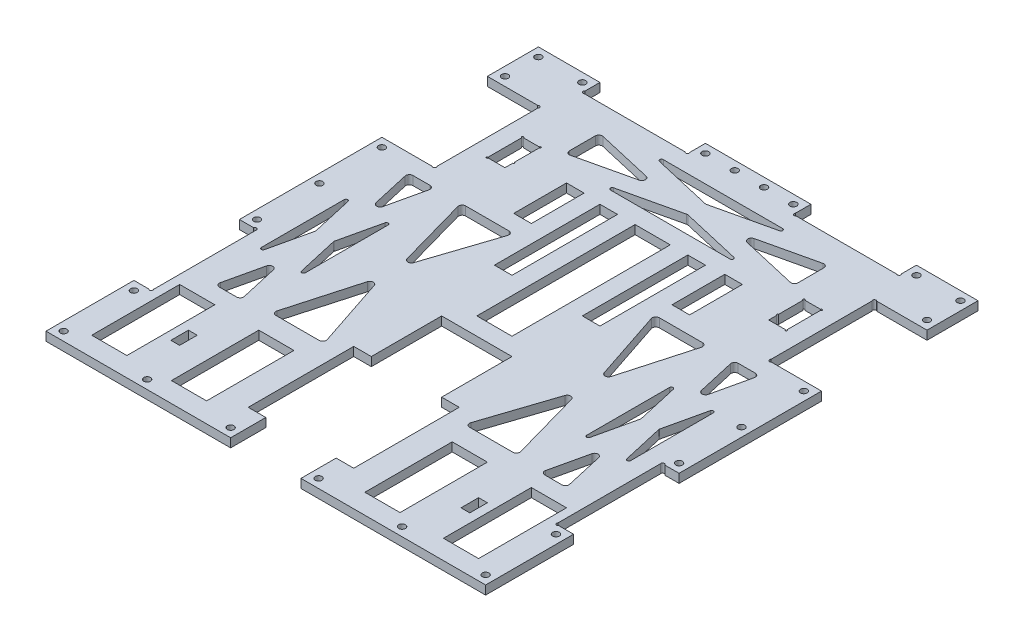
SolidWorks part; units mm, degrees
material "7050-T73510"
ref_plane "Front Plane" through (0, 0, 0) normal (0, 0, 1) x (1, 0, 0)
ref_plane "Top Plane" through (0, 0, 0) normal (0, 1, 0) x (1, 0, 0)
ref_plane "Right Plane" through (0, 0, 0) normal (1, 0, 0) x (0, 0, -1)
sketch "Sketch1" plane through (0, 0, 0) normal (0, 1, 0) x (1, 0, 0)
  line L1 (-158.75, -177.8) -> (158.75, -177.8)
  line L2 (-158.75, -177.8) -> (-158.75, 177.8)
  line L3 (-158.75, 177.8) -> (158.75, 177.8)
  line L4 (158.75, -177.8) -> (158.75, 177.8)
  line L5 (-158.75, -177.8) -> (158.75, 177.8) construction
  line L6 (-158.75, 177.8) -> (158.75, -177.8) construction
  point P0 (0, 0)
  dimension "D1" = 355.6
  dimension "D2" = 317.5
extrude "Boss-Extrude1" add sketch "Sketch1" along normal blind 6.35
sketch "Sketch2" plane through (0, 6.35, 0) normal (0, 1, 0) x (1, 0, 0)
  line L0 (-158.75, -177.8) -> (158.75, -177.8) construction
  line L1 (-25.4, -25.4) -> (25.4, -25.4)
  line L2 (-25.4, -25.4) -> (-25.4, -177.8)
  line L3 (-25.4, -177.8) -> (25.4, -177.8)
  line L4 (25.4, -25.4) -> (25.4, -177.8)
  line L5 (-25.4, -25.4) -> (25.4, -177.8) construction
  line L6 (-25.4, -177.8) -> (25.4, -25.4) construction
  point P0 (0, -101.6)
  dimension "D1" = 152.4
  dimension "D2" = 50.8
extrude "Cut-Extrude1" cut sketch "Sketch2" against normal through all
sketch "Sketch3" plane through (0, 6.35, 0) normal (0, 1, 0) x (1, 0, 0)
  line L0 (158.75, -177.8) -> (158.75, 177.8) construction
  line L5 (146.05, 140.97) -> (120.65, 140.97)
  line L11 (146.05, 140.97) -> (146.05, 64.77)
  line L13 (146.05, 64.77) -> (120.65, 64.77)
  line L15 (120.65, 140.97) -> (120.65, 64.77)
  line L16 (158.75, 177.8) -> (-158.75, 177.8) construction
  line L17 (107.95, 90.17) -> (95.25, 90.17)
  line L18 (107.95, 90.17) -> (107.95, 115.57)
  line L19 (107.95, 115.57) -> (95.25, 115.57)
  line L20 (95.25, 90.17) -> (95.25, 115.57)
  line L21 (0, -3.4925) -> (0, 3.4925) construction
  line L22 (-95.25, 90.17) -> (-95.25, 115.57)
  line L23 (-107.95, 115.57) -> (-95.25, 115.57)
  line L24 (-107.95, 90.17) -> (-107.95, 115.57)
  line L25 (-107.95, 90.17) -> (-95.25, 90.17)
  line L26 (-120.65, 140.97) -> (-120.65, 64.77)
  line L27 (-146.05, 64.77) -> (-120.65, 64.77)
  line L28 (-146.05, 140.97) -> (-146.05, 64.77)
  line L29 (-146.05, 140.97) -> (-120.65, 140.97)
  point P14 (107.95, 102.87)
  point P15 (120.65, 102.87)
  dimension "D1" = 25.4
  dimension "D2" = 12.7
  dimension "D3" = 12.7
  dimension "D4" = 12.7
  dimension "D5" = 25.4
  dimension "D6" = 76.2
  dimension "D7" = 36.83
extrude "Cut-Extrude2" cut sketch "Sketch3" against normal through all contours L5 L15 L13 L11 | L20 L17 L18 L19 | L29 L28 L27 L26 | L24 L25 L22 L23 | L26 L27 L28 L29 region at (133.35, 6.35, -102.87) region at (101.6, 6.35, -102.87) region at (-101.6, 6.35, -102.87) region at (-133.35, 6.35, -102.87)
sketch "Sketch4" plane through (0, 6.35, 0) normal (0, 1, 0) x (1, 0, 0)
  line L0 (-158.75, 177.8) -> (-158.75, -177.8) construction
  line L1 (-158.75, 140.97) -> (-146.05, 140.97)
  line L2 (-158.75, 140.97) -> (-158.75, 64.77)
  line L3 (-158.75, 64.77) -> (-146.05, 64.77)
  line L4 (-146.05, 140.97) -> (-146.05, 64.77)
  line L5 (0, -3.4925) -> (0, 3.4925) construction
  line L6 (-158.75, -114.3) -> (-146.05, -114.3)
  line L7 (-158.75, -114.3) -> (-158.75, -38.1)
  line L8 (-158.75, -38.1) -> (-146.05, -38.1)
  line L9 (-146.05, -114.3) -> (-146.05, -38.1)
  line L10 (158.75, 64.77) -> (146.05, 64.77)
  line L11 (146.05, 140.97) -> (146.05, 64.77)
  line L12 (158.75, 140.97) -> (146.05, 140.97)
  line L13 (158.75, 140.97) -> (158.75, 64.77)
  line L14 (158.75, -38.1) -> (146.05, -38.1)
  line L15 (146.05, -114.3) -> (146.05, -38.1)
  line L16 (158.75, -114.3) -> (146.05, -114.3)
  line L17 (158.75, -114.3) -> (158.75, -38.1)
  line L18 (158.75, 177.8) -> (-158.75, 177.8) construction
  line L19 (114.3, 165.1) -> (38.1, 165.1)
  line L20 (-114.3, 177.8) -> (-38.1, 177.8)
  line L21 (-114.3, 177.8) -> (-114.3, 165.1)
  line L22 (-114.3, 165.1) -> (-38.1, 165.1)
  line L23 (-38.1, 177.8) -> (-38.1, 165.1)
  line L24 (38.1, 177.8) -> (38.1, 165.1)
  line L25 (114.3, 177.8) -> (38.1, 177.8)
  line L26 (114.3, 177.8) -> (114.3, 165.1)
  line L27 (-25.4, -25.4) -> (-25.4, -177.8) construction
  line L28 (-25.4, -152.4) -> (-38.1, -152.4)
  line L29 (-25.4, -152.4) -> (-25.4, -76.2)
  line L30 (-25.4, -76.2) -> (-38.1, -76.2)
  line L31 (-38.1, -152.4) -> (-38.1, -76.2)
  line L32 (-158.75, -177.8) -> (-25.4, -177.8) construction
  line L33 (25.4, 101.6) -> (38.1, 101.6)
  line L34 (-25.4, 25.4) -> (-38.1, 25.4)
  line L35 (-25.4, 25.4) -> (-25.4, 101.6)
  line L36 (-25.4, 101.6) -> (-38.1, 101.6)
  line L37 (-38.1, 25.4) -> (-38.1, 101.6)
  line L38 (38.1, 25.4) -> (38.1, 101.6)
  line L39 (25.4, 25.4) -> (38.1, 25.4)
  line L40 (25.4, 25.4) -> (25.4, 101.6)
  line L41 (25.4, -76.2) -> (38.1, -76.2)
  line L42 (38.1, -152.4) -> (38.1, -76.2)
  line L43 (25.4, -152.4) -> (38.1, -152.4)
  line L44 (25.4, -152.4) -> (25.4, -76.2)
  dimension "D1" = 12.7
  dimension "D2" = 12.7
  dimension "D3" = 76.2
  dimension "D4" = 76.2
  dimension "D5" = 36.83
  dimension "D6" = 215.9
  dimension "D7" = 12.7
  dimension "D8" = 76.2
  dimension "D9" = 76.2
  dimension "D10" = 12.7
  dimension "D11" = 76.2
  dimension "D12" = 25.4
  dimension "D13" = 76.2
  dimension "D14" = 12.7
  dimension "D15" = 203.2
  dimension "D16" = 50.8
extrude "Cut-Extrude3" cut sketch "Sketch4" against normal through all
sketch "Sketch5" plane through (0, 6.35, 0) normal (0, 1, 0) x (1, 0, 0)
  line L0 (-38.1, -76.2) -> (-38.1, -152.4) construction
  line L5 (-38.1, 101.6) -> (-38.1, 25.4) construction
  line L6 (-82.55, -100.33) -> (-57.15, -100.33)
  line L7 (-133.35, -87.63) -> (-101.6, -87.63)
  line L8 (-133.35, -87.63) -> (-133.35, 52.07)
  line L9 (-133.35, 52.07) -> (-101.6, 52.07)
  line L10 (-101.6, -87.63) -> (-101.6, 52.07)
  line L11 (-133.35, -87.63) -> (-101.6, 52.07) construction
  line L12 (-133.35, 52.07) -> (-101.6, -87.63) construction
  line L13 (-82.55, 114.3) -> (82.55, 114.3)
  line L14 (-82.55, 114.3) -> (-82.55, 152.4)
  line L15 (-82.55, 152.4) -> (82.55, 152.4)
  line L16 (82.55, 114.3) -> (82.55, 152.4)
  line L17 (-82.55, 114.3) -> (82.55, 152.4) construction
  line L18 (-82.55, 152.4) -> (82.55, 114.3) construction
  line L23 (0, -3.4925) -> (0, 3.4925) construction
  line L24 (-12.7, -12.7) -> (12.7, -12.7)
  line L25 (-146.05, -114.3) -> (-146.05, -38.1) construction
  line L26 (-50.8, 102.87) -> (-63.5, 102.87)
  line L27 (-50.8, 102.87) -> (-50.8, 64.77)
  line L28 (-158.75, 64.77) -> (-158.75, -38.1) construction
  line L29 (-158.75, 64.77) -> (-120.65, 64.77) construction
  line L30 (-82.55, -100.33) -> (-82.55, -163.4194)
  line L31 (-12.7, -12.7) -> (-12.7, 101.6)
  line L32 (-12.7, 101.6) -> (12.7, 101.6)
  line L33 (12.7, -12.7) -> (12.7, 101.6)
  line L34 (-50.8, 64.77) -> (-63.5, 64.77)
  line L35 (-63.5, 102.87) -> (-63.5, 64.77)
  line L36 (50.8, 64.77) -> (63.5, 64.77)
  line L37 (-25.4, 25.4) -> (-25.4, 101.6) construction
  line L38 (-25.4, 101.6) -> (-38.1, 101.6) construction
  line L39 (-95.25, 90.17) -> (-95.25, 115.57) construction
  line L40 (-114.3, 165.1) -> (-38.1, 165.1) construction
  line L41 (-82.55, -163.4194) -> (-57.15, -163.4194)
  line L42 (-57.15, -100.33) -> (-57.15, -163.4194)
  line L43 (-139.5421, 50.6627) -> (-107.7921, -89.0373)
  line L44 (-127.1579, -89.0373) -> (-95.4079, 50.6627)
  line L45 (63.5, 102.87) -> (63.5, 64.77)
  line L46 (50.8, 102.87) -> (63.5, 102.87)
  line L47 (-83.9779, 146.2126) -> (81.1221, 108.1126)
  line L48 (-81.1221, 108.1126) -> (83.9779, 146.2126)
  line L49 (50.8, 102.87) -> (50.8, 64.77)
  line L50 (-88.9, -16.4414) -> (-50.8, -16.4414) construction
  line L51 (-127.1579, 53.4773) -> (-95.4079, -86.2227)
  line L52 (-139.5421, -86.2227) -> (-107.7921, 53.4773)
  line L53 (-88.9, 52.07) -> (-50.8, 52.07) construction
  line L54 (-88.9, 52.07) -> (-88.9, -84.9527) construction
  line L55 (-81.1221, 158.5874) -> (83.9779, 120.4874)
  line L56 (-83.9779, 120.4874) -> (81.1221, 158.5874)
  line L57 (-139.7, -100.33) -> (-114.3, -100.33)
  line L58 (-139.7, -100.33) -> (-139.7, -163.83)
  line L59 (-139.7, -163.83) -> (-114.3, -163.83)
  line L60 (-114.3, -100.33) -> (-114.3, -163.83)
  line L61 (-88.9, -84.9527) -> (-50.8, -84.9527)
  line L62 (-50.8, 52.07) -> (-50.8, -84.9527) construction
  line L63 (-107.95, -138.43) -> (-101.6, -138.43)
  line L64 (-107.95, -138.43) -> (-107.95, -125.73)
  line L65 (-107.95, -125.73) -> (-101.6, -125.73)
  line L66 (-101.6, -138.43) -> (-101.6, -125.73)
  line L67 (-107.95, -138.43) -> (-101.6, -125.73) construction
  line L68 (-107.95, -125.73) -> (-101.6, -138.43) construction
  line L69 (-88.9, -84.9527) -> (-71.4375, -22.7914)
  line L70 (-71.4375, -22.7914) -> (-50.8, -84.9527)
  line L71 (-88.9, 52.07) -> (-50.8, 52.07)
  line L72 (-88.9, 52.07) -> (-71.4375, -10.0914)
  line L73 (-71.4375, -10.0914) -> (-50.8, 52.07)
  point P5 (-117.475, -17.78)
  point P10 (0, 133.35)
  point P15 (0, 44.45)
  point P34 (-104.775, -132.08)
  point P45 (-31.75, 101.6)
  point P87 (-114.3, -132.08)
  dimension "D3" = 12.7
  dimension "D4" = 19.05
  dimension "D5" = 139.7
  dimension "D6" = 25.4
  dimension "D7" = 12.7
  dimension "D8" = 31.75
  dimension "D9" = 25.4
  dimension "D10" = 12.7
  dimension "D11" = 165.1
  dimension "D12" = 12.7
  dimension "D13" = 12.7
  dimension "D14" = 12.7
  dimension "D17" = 25.4
  dimension "D18" = 63.5
  dimension "D19" = 12.7
  dimension "D20" = 6.35
  dimension "D21" = 38.1
  dimension "D22" = 38.1
  dimension "D23" = 12.7
  dimension "D15" = 114.3
  dimension "D16" = 12.7
  dimension "D24" = 12.7
  dimension "D25" = 12.7
  dimension "D26" = 12.7
  dimension "D27" = 15.3773
  dimension "D28" = 12.7
  dimension "D29" = 6.35
  dimension "D30" = 12.7
extrude "Cut-Extrude4" cut sketch "Sketch5" against normal through all contours L44 L7 L43 | L8 L52 L43 | L51 L52 L9 | L44 L51 L10 | L33 | L32 | L31 | L24 | L48 L13 L47 | L48 L55 L16 | L55 L56 L15 | L14 L56 L47 | L60 L57 L58 L59 | L63 L66 L65 L64 | L42 L6 L30 L41 | L26 L35 L34 L27 | L46 L49 L36 L45 | L61 L70 L69 | L71 L73 L72 region at (-69.85, 6.35, 131.8747) region at (-117.475, 6.35, 73.8975) region at (-130.229, 6.35, 17.78) region at (-104.721, 6.35, 17.78) region at (-117.475, 6.35, -38.3375) region at (0, 6.35, -118.4777) region at (-64.4466, 6.35, -133.35) region at (64.4466, 6.35, -133.35) region at (0, 6.35, -148.2223) region at (0, 6.35, -44.45) region at (-57.15, 6.35, -83.82) region at (57.15, 6.35, -83.82) region at (-127, 6.35, 132.08) region at (-104.775, 6.35, 132.08)
mirror "Mirror1" about plane through (0, 0, 0) normal (1, 0, 0) of "Cut-Extrude4"
sketch "Sketch7" plane through (0, 6.35, 0) normal (0, 1, 0) x (1, 0, 0)
  line L0 (-158.75, -177.8) -> (-25.4, -177.8) construction
  line L1 (-158.75, -114.3) -> (-158.75, -177.8) construction
  line L2 (0, -3.4925) -> (0, 3.4925) construction
  line L3 (-158.75, 177.8) -> (-158.75, 140.97) construction
  line L4 (-114.3, 177.8) -> (-158.75, 177.8) construction
  line L6 (38.1, 177.8) -> (-38.1, 177.8) construction
  line L7 (-38.1, 165.1) -> (-38.1, 177.8) construction
  line L8 (-25.4, -152.4) -> (-25.4, -177.8) construction
  line L9 (-158.75, -114.3) -> (-146.05, -114.3) construction
  line L10 (-158.75, 64.77) -> (-158.75, -38.1) construction
  line L11 (-146.05, -38.1) -> (-158.75, -38.1) construction
  line L12 (-158.75, 64.77) -> (-120.65, 64.77) construction
  circle A0 centre (-152.4, -171.45) radius 2.413
  circle A14 centre (-152.4, 171.45) radius 2.413
  circle A15 centre (-120.65, 171.45) radius 2.413
  circle A16 centre (-152.4, 147.32) radius 2.413
  circle A34 centre (-31.75, 171.45) radius 2.413
  circle A35 centre (-10.5833, 171.45) radius 2.413
  circle A36 centre (10.5833, 171.45) radius 2.413
  circle A37 centre (31.75, 171.45) radius 2.413
  circle A38 centre (-31.75, -171.45) radius 2.413
  circle A39 centre (-92.075, -171.45) radius 2.413
  circle A40 centre (-152.4, -120.65) radius 2.413
  circle A41 centre (-152.4, -31.75) radius 2.413
  circle A42 centre (-152.4, 58.42) radius 2.413
  circle A43 centre (-152.4, 13.335) radius 2.413
  circle A44 centre (31.75, -171.45) radius 2.413
  circle A45 centre (152.4, 13.335) radius 2.413
  circle A46 centre (152.4, 58.42) radius 2.413
  circle A47 centre (152.4, -31.75) radius 2.413
  circle A48 centre (152.4, -120.65) radius 2.413
  circle A49 centre (92.075, -171.45) radius 2.413
  circle A50 centre (152.4, 147.32) radius 2.413
  circle A51 centre (120.65, 171.45) radius 2.413
  circle A52 centre (152.4, 171.45) radius 2.413
  circle A53 centre (152.4, -171.45) radius 2.413
  dimension "D1" = 4.826
  dimension "D6" = 6.35
  dimension "D9" = 4.826
  dimension "D14" = 4.826
  dimension "D4" = 4.826
  dimension "D5" = 4.826
  dimension "D8" = 4.826
  dimension "D20" = 4.826
  dimension "D24" = 4.826
  dimension "D25" = 4.826
  dimension "D2" = 6.35
  dimension "D3" = 6.35
  dimension "D7" = 60.325
  dimension "D10" = 6.35
  dimension "D11" = 6.35
  dimension "D15" = 6.35
  dimension "D16" = 6.35
  dimension "D18" = 6.35
  dimension "D19" = 6.35
  dimension "D21" = 6.35
  dimension "D22" = 6.35
  dimension "D23" = 6.35
  dimension "D26" = 45.085
  dimension "D12" = 2
  dimension "D13" = 2
  dimension "D17" = 4
extrude "Cut-Extrude6" cut sketch "Sketch7" against normal through all
sketch "Sketch8" plane through (0, 6.35, 0) normal (0, 1, 0) x (1, 0, 0)
  line L0 (-107.95, 115.57) -> (-95.25, 115.57) construction
  line L1 (-107.95, 90.17) -> (-107.95, 115.57) construction
  line L2 (-95.25, 90.17) -> (-95.25, 115.57) construction
  line L3 (0, -3.4925) -> (0, 3.4925) construction
  circle A0 centre (-39.0994, 165.8837) radius 1.27
  circle A1 centre (-113.5398, 166.1174) radius 1.27
  circle A2 centre (-121.56, 140.0841) radius 1.27
  circle A3 centre (-121.5656, 65.6501) radius 1.27
  circle A4 centre (-147.253, -38.507) radius 1.27
  circle A5 centre (-147.0444, -113.51) radius 1.27
  circle A11 centre (-107.95, 115.57) radius 0.635
  circle A12 centre (-95.25, 115.57) radius 0.635
  circle A13 centre (-95.25, 96.52) radius 0.635
  circle A14 centre (-107.95, 90.17) radius 0.635
  circle A15 centre (107.95, 90.17) radius 0.635
  circle A16 centre (95.25, 96.52) radius 0.635
  circle A17 centre (95.25, 115.57) radius 0.635
  circle A18 centre (107.95, 115.57) radius 0.635
  dimension "D1" = 1.27
  dimension "D2" = 1.27
  dimension "D3" = 1.27
  dimension "D4" = 1.27
extrude "Cut-Extrude7" cut sketch "Sketch8" against normal through all
mirror "Mirror2" about plane through (0, 0, 0) normal (1, 0, 0) of "Cut-Extrude7"
fillet "Fillet1" radius 1.27 16 edges at (-101.6, 3.175, 58.9775) (-110.9631, 3.175, 17.78) (-101.6, 3.175, -23.4175) (-133.35, 3.175, -23.4175) (-123.9869, 3.175, 17.78) (-133.35, 3.175, 58.9775) (133.35, 3.175, -23.4175) (133.35, 3.175, 58.9775) (123.9869, 3.175, 17.78) (101.6, 3.175, -23.4175) (110.9631, 3.175, 17.78) (101.6, 3.175, 58.9775) (54.3101, 3.175, -152.4) (-54.3101, 3.175, -152.4) (54.3101, 3.175, -114.3) (-54.3101, 3.175, -114.3)
fillet "Fillet2" radius 2.54 32 edges at (-126.8381, 3.175, 87.63) (-108.1119, 3.175, 87.63) (-117.475, 3.175, 46.4325) (-28.2399, 3.175, -133.35) (-82.55, 3.175, -120.8169) (-82.55, 3.175, -145.8831) (-88.9, 3.175, -52.07) (-71.4375, 3.175, 10.0914) (-50.8, 3.175, -52.07) (-71.4375, 3.175, 22.7914) (-88.9, 3.175, 84.9527) (-50.8, 3.175, 84.9527) (-126.8381, 3.175, -52.07) (-117.475, 3.175, -10.8725) (-108.1119, 3.175, -52.07) (126.8381, 3.175, 87.63) (108.1119, 3.175, 87.63) (117.475, 3.175, 46.4325) (88.9, 3.175, 84.9527) (50.8, 3.175, 84.9527) (71.4375, 3.175, 22.7914) (117.475, 3.175, -10.8725) (108.1119, 3.175, -52.07) (126.8381, 3.175, -52.07) (71.4375, 3.175, 10.0914) (88.9, 3.175, -52.07) (50.8, 3.175, -52.07) (28.2399, 3.175, -133.35) (82.55, 3.175, -120.8169) (82.55, 3.175, -145.8831) (0, 3.175, -139.8669) (0, 3.175, -126.8331)
